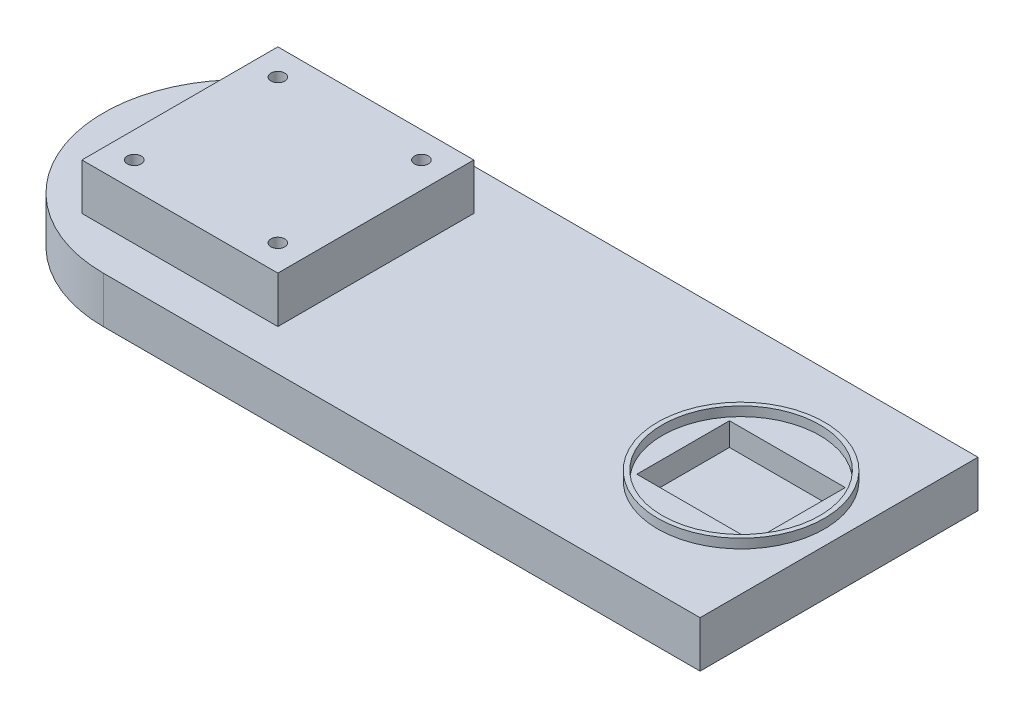
SolidWorks part; units mm, degrees
ref_plane "Front Plane" through (0, 0, 0) normal (0, 0, 1) x (1, 0, 0)
ref_plane "Top Plane" through (0, 0, 0) normal (0, 1, 0) x (1, 0, 0)
ref_plane "Right Plane" through (0, 0, 0) normal (1, 0, 0) x (0, 0, -1)
sketch "Sketch2" plane through (0, 0, 0) normal (0, 1, 0) x (1, 0, 0)
  line L0 (-7.6378, -30) -> (121.15, -30)
  line L1 (-15.5, 15.5) -> (15.5, 15.5) construction
  line L2 (-15.5, 15.5) -> (-15.5, -15.5) construction
  line L3 (-15.5, -15.5) -> (15.5, -15.5) construction
  line L4 (15.5, 15.5) -> (15.5, -15.5) construction
  line L5 (-15.5, 15.5) -> (15.5, -15.5) construction
  line L6 (-15.5, -15.5) -> (15.5, 15.5) construction
  line L7 (-21.15, 21.15) -> (21.15, 21.15)
  line L8 (-21.15, 21.15) -> (-21.15, -21.15)
  line L9 (-21.15, -21.15) -> (21.15, -21.15)
  line L10 (21.15, 21.15) -> (21.15, -21.15)
  line L11 (-21.15, 21.15) -> (21.15, -21.15) construction
  line L12 (-21.15, -21.15) -> (21.15, 21.15) construction
  line L13 (-7.6378, 30) -> (121.15, 30)
  line L14 (-21.15, -21.15) -> (-24.6855, -24.6855) construction
  line L15 (121.15, 30) -> (121.15, -30)
  circle A0 centre (-15.5, 15.5) radius 1.5
  circle A1 centre (15.5, 15.5) radius 1.5
  circle A2 centre (15.5, -15.5) radius 1.5
  circle A3 centre (-15.5, -15.5) radius 1.5
  arc A5 (-7.6378, 30) -> (-7.6378, -30) centre (-7.6378, 0) ccw
  point P0 (0, 0)
  point P10 (0, 0)
  dimension "D3" = 3
  dimension "D5" = 60
  dimension "D1" = 31
  dimension "D2" = 31
  dimension "D4" = 42.3
  dimension "D6" = 5
  dimension "D7" = 100
extrude "Boss-Extrude1" add sketch "Sketch2" along normal blind 10 contours L13 A5 L0 L15 L7 L10 L9 L8 | L10 L7 L8 L9 A3 A2 A1 A0 | L15 L0 A5 L13 region at (55.7384, 0, 0) region at (0, 0, 0)
sketch "Sketch3" plane through (0, 10, 0) normal (0, 1, 0) x (1, 0, 0)
  line L0 (0, 0) -> (100, 0) construction
  line L1 (-15.5, 15.5) -> (15.5, -15.5) construction
  line L3 (87.5, 10) -> (112.5, 10)
  line L4 (87.5, 10) -> (87.5, -10)
  line L5 (87.5, -10) -> (112.5, -10)
  line L6 (112.5, 10) -> (112.5, -10)
  line L7 (87.5, 10) -> (112.5, -10) construction
  line L8 (87.5, -10) -> (112.5, 10) construction
  dimension "D1" = 100
  dimension "D2" = 25
  dimension "D3" = 20
extrude "Cut-Extrude1" cut sketch "Sketch3" against normal blind 5
sketch "Sketch5" plane through (0, 10, 0) normal (0, 1, 0) x (1, 0, 0)
  line L0 (87.5, 0) -> (112.5, 0) construction
  line L1 (100, -10) -> (100, 10) construction
  line L4 (112.5, -10) -> (112.5, 10)
  line L5 (112.5, 10) -> (87.5, 10)
  line L6 (87.5, 10) -> (87.5, -10)
  line L7 (87.5, -10) -> (112.5, -10)
  line L8 (112.5, -10) -> (112.5, 10) construction
  line L9 (112.5, 10) -> (87.5, 10) construction
  line L10 (87.5, 10) -> (87.5, -10) construction
  line L11 (87.5, -10) -> (112.5, -10) construction
  circle A0 centre (100, 0) radius 17
  circle A1 centre (100, 0) radius 18
  dimension "D3" = 34
  dimension "D1" = 0
  dimension "D2" = 1
extrude "Boss-Extrude2" add sketch "Sketch5" along normal blind 2
extrude "Boss-Extrude3" add sketch "Sketch2<3>" along normal blind 20 contours L10 L7 L8 L9 A3 A2 A1 A0 region at (0, 0, 0)
sketch "Sketch2<3>" plane through (0, 0, 0) normal (0, 1, 0) x (1, 0, 0) same geometry as "Sketch2"
extrude "Cut-Extrude2" cut sketch "Sketch2<4>" against normal through all both and the other way through all contours A3 | A0 | A1 | A2 region at (-15.5, 0, -15.5) region at (15.5, 0, -15.5) region at (15.5, 0, 15.5) region at (-15.5, 0, 15.5)
sketch "Sketch2<4>" plane through (0, 0, 0) normal (0, 1, 0) x (1, 0, 0) same geometry as "Sketch2"
